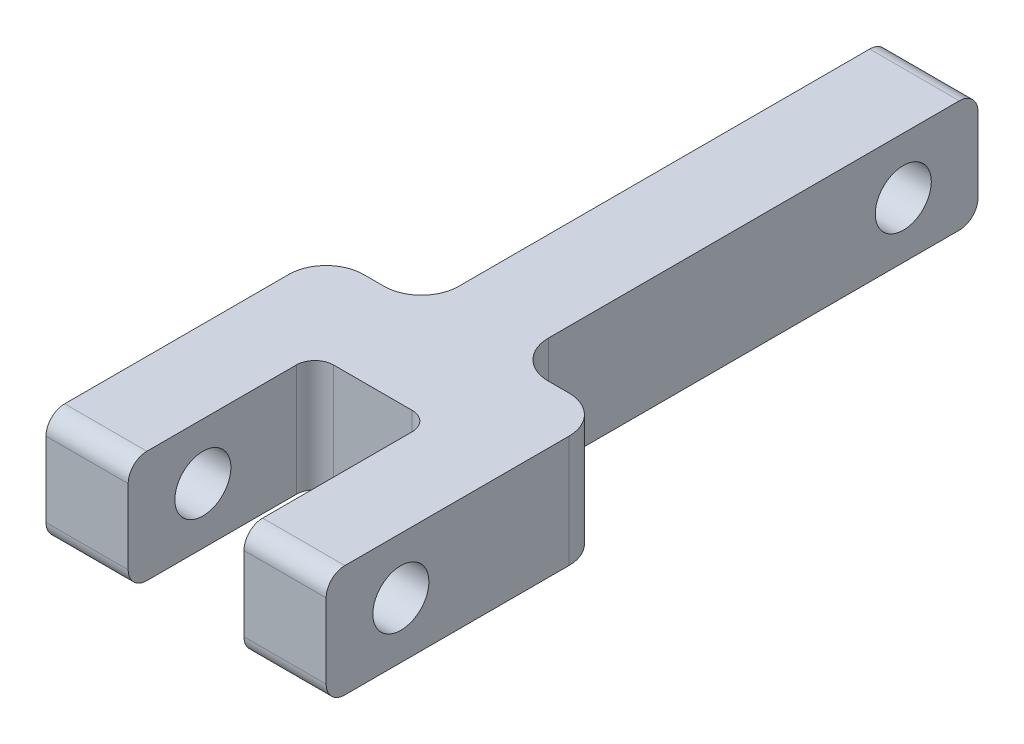
SolidWorks part; units mm, degrees
ref_plane "Alzado" through (0, 0, 0) normal (0, 0, 1) x (1, 0, 0)
ref_plane "Planta" through (0, 0, 0) normal (0, 1, 0) x (1, 0, 0)
ref_plane "Vista lateral" through (0, 0, 0) normal (1, 0, 0) x (0, 0, -1)
sketch "Croquis1" plane through (0, 0, 0) normal (1, 0, 0) x (0, 0, -1)
  line L0 (-19, 3) -> (19, 3)
  line L2 (-20, 0) -> (20, 0) construction
  line L3 (-20, 2) -> (-20, -2)
  line L4 (-19, -3) -> (19, -3)
  line L5 (20, 2) -> (20, -2)
  arc A0 (-20, -2) -> (-19, -3) centre (-19, -2) ccw
  arc A1 (-20, 2) -> (-19, 3) centre (-19, 2) cw
  arc A2 (19, -3) -> (20, -2) centre (19, -2) ccw
  arc A3 (19, 3) -> (20, 2) centre (19, 2) cw
  point P1 (0, 0)
  point P9 (-20, -3)
  point P13 (-20, 3)
  point P16 (20, -3)
  point P19 (20, 3)
  dimension "D3" = 1
  dimension "D4" = 1
  dimension "D1" = 3
  dimension "D2" = 40
extrude "Saliente-Extruir1" add sketch "Croquis1" along normal mid plane 4.8
sketch "Croquis2" plane through (0, 0, 0) normal (1, 0, 0) x (0, 0, -1)
  line L0 (-20, 2) -> (-20, -2) construction
  line L1 (20, -2) -> (20, 2) construction
  circle A0 centre (-16, 0) radius 1.5
  circle A1 centre (16, 0) radius 1.5
  dimension "D1" = 3
  dimension "D3" = 3
  dimension "D2" = 4
  dimension "D4" = 4
extrude "Cortar-Extruir1" cut sketch "Croquis2" against normal through all both and the other way through all
sketch "Croquis3" plane through (0, 0, 0) normal (1, 0, 0) x (0, 0, -1)
  line L0 (-20, 2) -> (-20, -2) construction
  line L1 (-20, 2) -> (-20, -2)
  line L2 (-19, 3) -> (-5, 3)
  line L3 (19, 3) -> (-19, 3) construction
  line L4 (-5, 3) -> (-5, -3)
  line L5 (-19, -3) -> (19, -3) construction
  line L6 (-5, -3) -> (-19, -3)
  circle A0 centre (-16, 0) radius 1.5 construction
  circle A1 centre (-16, 0) radius 1.5
  arc A2 (-19, 3) -> (-20, 2) centre (-19, 2) ccw construction
  arc A3 (-19, 3) -> (-20, 2) centre (-19, 2) ccw
  arc A4 (-20, -2) -> (-19, -3) centre (-19, -2) ccw construction
  arc A5 (-20, -2) -> (-19, -3) centre (-19, -2) ccw
  dimension "D1" = 15
extrude "Saliente-Extruir2" add sketch "Croquis3" along normal mid plane 15
sketch "Croquis4" plane through (0, 0, 0) normal (1, 0, 0) x (0, 0, -1)
  line L0 (-19, 3) -> (-10, 3)
  line L1 (-5, 3) -> (-19, 3) construction
  line L2 (-10, 3) -> (-10, -3)
  line L3 (-19, -3) -> (-5, -3) construction
  line L4 (-20, 2) -> (-20, -2)
  line L5 (-19, -3) -> (-5, -3)
  line L6 (-5, -3) -> (-5, 3)
  line L7 (-5, 3) -> (-19, 3)
  line L8 (-20, 2) -> (-20, -2)
  line L12 (-10, -3) -> (-19, -3)
  arc A2 (-19, 3) -> (-20, 2) centre (-19, 2) ccw
  arc A3 (-20, -2) -> (-19, -3) centre (-19, -2) ccw
  arc A4 (-19, 3) -> (-20, 2) centre (-19, 2) ccw
  arc A5 (-20, -2) -> (-19, -3) centre (-19, -2) ccw
  dimension "D2" = 10
  dimension "D1" = 0
extrude "Cortar-Extruir2" cut sketch "Croquis4" against normal mid plane 6.2
fillet "Redondeo1" radius 2 4 edges at (2.4, 0, 5) (-2.4, 0, 5) (7.5, 0, 5) (-7.5, 0, 5)
fillet "Redondeo2" radius 1 2 edges at (3.1, 0, 10) (-3.1, 0, 10)
